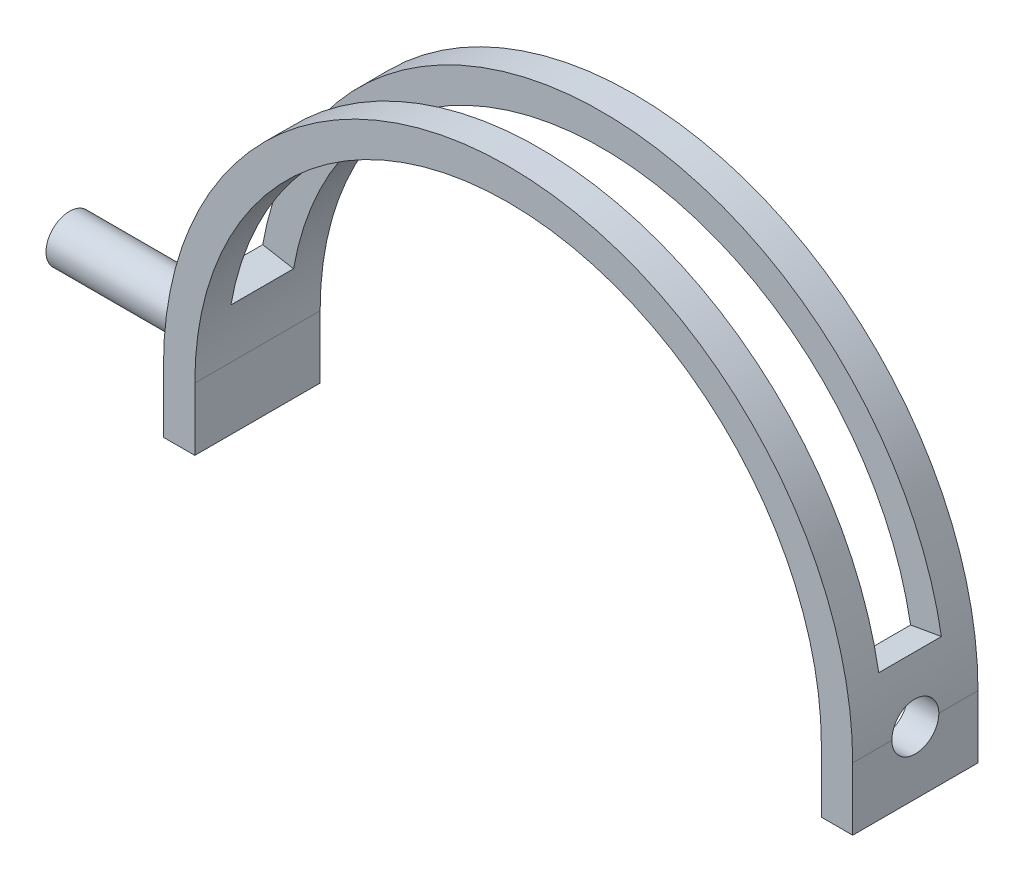
SolidWorks part; units mm, degrees
ref_plane "Front Plane" through (0, 0, 0) normal (0, 0, 1) x (1, 0, 0)
ref_plane "Top Plane" through (0, 0, 0) normal (0, 1, 0) x (1, 0, 0)
ref_plane "Right Plane" through (0, 0, 0) normal (1, 0, 0) x (0, 0, -1)
sketch "Sketch1" plane through (0, 0, 0) normal (0, 0, 1) x (1, 0, 0)
  line L0 (0, 0) -> (0, -10) construction
  line L1 (-50, -10) -> (0, -10) construction
  line L2 (-55, -10) -> (-50, -10)
  line L3 (50, 0) -> (55, 0) construction
  line L4 (0, 0) -> (57.5135, 0) construction
  line L5 (0, 0) -> (0, 64.0038) construction
  line L6 (-55, 0) -> (-55, -10)
  line L7 (-50, -10) -> (-50, 0)
  line L8 (55, 0) -> (55, -10)
  line L9 (55, -10) -> (50, -10)
  line L10 (50, -10) -> (50, 0)
  arc A0 (55, 0) -> (-55, 0) centre (0, 0) ccw
  arc A1 (50, 0) -> (-50, 0) centre (0, 0) ccw
  dimension "D1" = 100
  dimension "D2" = 5
  dimension "D3" = 10
  dimension "D4" = 90
  dimension "D5" = 10
extrude "Boss-Extrude1" add sketch "Sketch1" along normal blind 10 and the other way blind 10
sketch "Sketch2" plane through (0, 0, 0) normal (0, 0, 1) x (1, 0, 0)
  line L0 (0, 0) -> (-54.1644, 9.5506)
  line L2 (54.1644, 9.5506) -> (0, 0)
  line L3 (50, 0) -> (55, 0) construction
  line L4 (-200000, 0) -> (200057.5135, 0) construction
  arc A0 (55, 0) -> (-55, 0) centre (0, 0) ccw construction
  arc A2 (54.1644, 9.5506) -> (-54.1644, 9.5506) centre (0, 0) ccw
  dimension "D1" = 10
  dimension "D2" = 10
extrude "Cut-Extrude1" cut sketch "Sketch2" against normal blind 5 and the other way blind 5
sketch "Sketch4" plane through (-55, 0, 0) normal (-1, 0, 0) x (0, 0, 1)
  circle A0 centre (0, 0) radius 3.75
  dimension "D1" = 7.5
extrude "Boss-Extrude2" add sketch "Sketch4" along normal blind 25
sketch "Sketch5" plane through (55, 0, 0) normal (1, 0, 0) x (0, 0, -1)
  circle A0 centre (0, 0) radius 3.75
  dimension "D1" = 7.5
extrude "Cut-Extrude3" cut sketch "Sketch5" against normal blind 25
ref_axis "Axis of rotation" through (-80, 0, 0) along (1, 0, 0)
